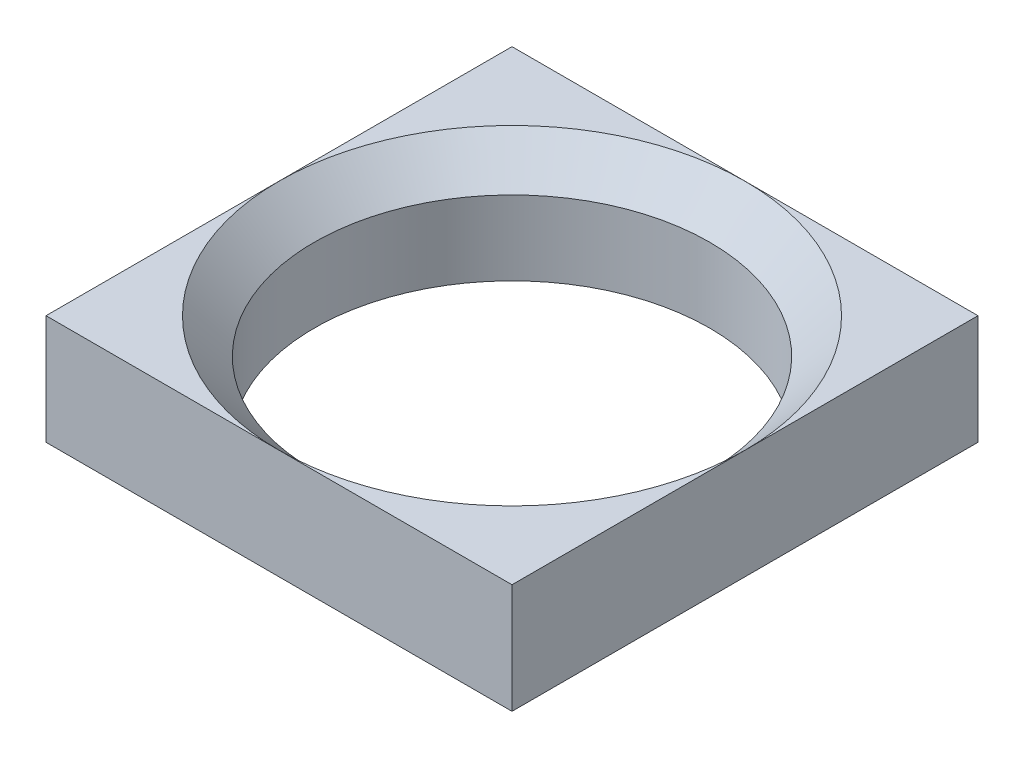
SolidWorks part; units mm, degrees
ref_plane "前视基准面" through (0, 0, 0) normal (0, 0, 1) x (1, 0, 0)
ref_plane "上视基准面" through (0, 0, 0) normal (0, 1, 0) x (1, 0, 0)
ref_plane "右视基准面" through (0, 0, 0) normal (1, 0, 0) x (0, 0, -1)
other "Configuration Table"
sketch "草图1" plane through (0, 0, 0) normal (0, 1, 0) x (1, 0, 0)
  line L1 (-5.95, 5.95) -> (5.95, 5.95)
  line L2 (-5.95, 5.95) -> (-5.95, -5.95)
  line L3 (-5.95, -5.95) -> (5.95, -5.95)
  line L4 (5.95, 5.95) -> (5.95, -5.95)
  line L5 (-5.95, 5.95) -> (5.95, -5.95) construction
  line L6 (-5.95, -5.95) -> (5.95, 5.95) construction
  circle A0 centre (0, 0) radius 5.05
  point P0 (0, 0)
  dimension "D1" = 10.1
  dimension "D2" = 11.9
extrude "凸台-拉伸1" add sketch "草图1" along normal blind 2.8
chamfer "倒角1" distance 0.9 angle 45 1 edges at (0, 2.8, 5.05)
